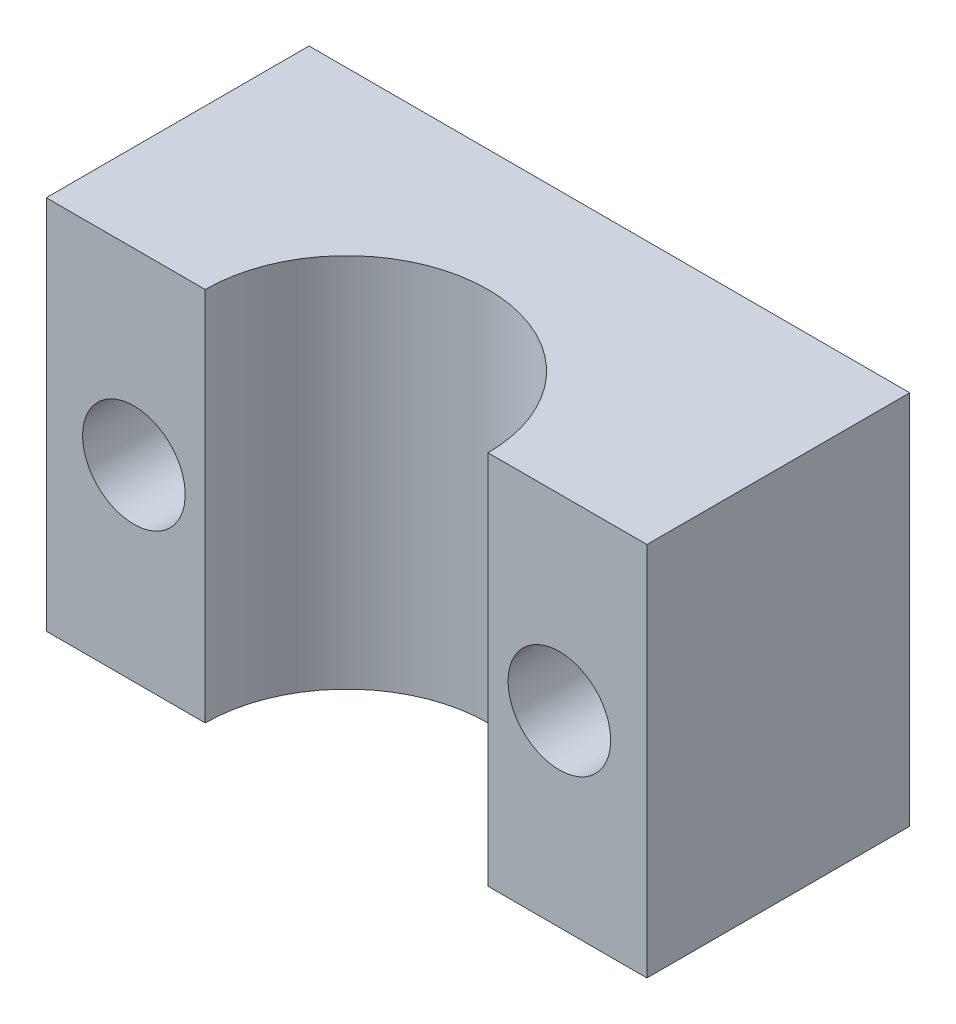
SolidWorks part; units mm, degrees
ref_plane "Спереди" through (0, 0, 0) normal (0, 0, 1) x (1, 0, 0)
ref_plane "Сверху" through (0, 0, 0) normal (0, 1, 0) x (1, 0, 0)
ref_plane "Справа" through (0, 0, 0) normal (1, 0, 0) x (0, 0, -1)
sketch "Эскиз1" plane through (0, 0, 0) normal (0, 1, 0) x (1, 0, 0)
  line L1 (-24, -10) -> (24, -10)
  line L2 (-24, -10) -> (-24, 10)
  line L3 (-24, 10) -> (24, 10)
  line L4 (24, -10) -> (24, 10)
  line L5 (-24, -10) -> (24, 10) construction
  line L6 (-24, 10) -> (24, -10) construction
  point P0 (0, 0)
  dimension "D1" = 48
  dimension "D2" = 20
extrude "Бобышка-Вытянуть1" add sketch "Эскиз1" along normal blind 30
sketch "Эскиз2" plane through (0, 0, 10) normal (0, 0, 1) x (1, 0, 0)
  line L0 (-7, 30) -> (-7, 0)
  line L1 (-24, 30) -> (24, 30) construction
  line L2 (-24, 0) -> (24, 0) construction
  line L3 (-7, 0) -> (7, 0)
  line L4 (7, 0) -> (7, 30)
  line L5 (7, 30) -> (-7, 30)
  dimension "D1" = 17
  dimension "D2" = 14
extrude "Вырез-Вытянуть1" cut sketch "Эскиз2" against normal blind 7
sketch "Эскиз7" plane through (24, 0, 0) normal (1, 0, 0) x (0, 0, -1)
  line L1 (32, 30) -> (32, 0)
  line L2 (32, 0) -> (10, 0)
  line L3 (-10, 0) -> (10, 0)
  line L4 (10, 0) -> (10.066, 0.2736)
  line L5 (10, 30) -> (32, 30)
  line L8 (10, 0) -> (10, 30)
  dimension "D3" = 22
extrude "Бобышка-Вытянуть2" add sketch "Эскиз7" against normal blind 48
sketch "Эскиз8" plane through (24, 0, 0) normal (1, 0, 0) x (0, 0, -1)
  line L0 (11, 0) -> (11, 30)
  line L1 (-10, 30) -> (32, 30) construction
  line L2 (11, 30) -> (32, 30)
  line L3 (11, 0) -> (32, 0)
  line L4 (32, 0) -> (32, 30)
  line L5 (-10, 0) -> (32, 0) construction
  point P16 (11, 0)
extrude "Вырез-Вытянуть2" cut sketch "Эскиз8" against normal blind 14
sketch "Эскиз9" plane through (-24, 0, 0) normal (-1, 0, 0) x (0, 0, 1)
  line L0 (-11, 0) -> (-11, 30)
  line L1 (-32, 30) -> (10, 30) construction
  line L2 (-11, 30) -> (-32, 30)
  line L3 (-32, 0) -> (10, 0) construction
  line L4 (-11, 0) -> (-32, 0)
  line L5 (-32, 0) -> (-32, 30)
  point P15 (-11, 0)
extrude "Вырез-Вытянуть3" cut sketch "Эскиз9" against normal blind 14
sketch "Эскиз11" plane through (-10, 0, 0) normal (-1, 0, 0) x (0, 0, 1)
  line L0 (-32, 30) -> (-11, 0) construction
  line L2 (-32, 0) -> (-11, 0) construction
  line L3 (-16.4, 4.9) -> (-16.4, 25.1)
  line L6 (-16.4, 4.9) -> (-26.6, 4.9)
  line L7 (-16.4, 25.1) -> (-26.6, 25.1)
  line L8 (-26.6, 4.9) -> (-26.6, 25.1)
  line L9 (-16.4, 4.9) -> (-26.6, 25.1) construction
  line L10 (-16.4, 25.1) -> (-26.6, 4.9) construction
  point P7 (-21.5, 15)
  point P8 (-21.5, 15)
  dimension "D1" = 20.2
  dimension "D2" = 10.2
extrude "Вырез-Вытянуть4" cut sketch "Эскиз11" against normal through all
sketch "Эскиз13" plane through (0, 0, -11) normal (0, 0, -1) x (-1, 0, 0)
  line L0 (24, 15) -> (10, 15) construction
  line L1 (24, 0) -> (24, 30) construction
  line L2 (10, 0) -> (10, 30) construction
  line L3 (-10, 15) -> (-24, 15) construction
  line L4 (-10, 30) -> (-10, 0) construction
  line L5 (-24, 30) -> (-24, 0) construction
  circle A0 centre (17, 15) radius 4.1
  circle A1 centre (-17, 15) radius 4.1
  dimension "D1" = 8.2
extrude "Вырез-Вытянуть5" cut sketch "Эскиз13" against normal through all
fillet "Скругление1" radius 7 2 edges at (-7, 15, 3) (7, 15, 3)
sketch "Sketch1" plane through (10, 0, 0) normal (1, 0, 0) x (0, 0, -1)
  line L0 (16.4, 25.1) -> (26.6, 4.9) construction
  line L2 (26.6, 4.9) -> (16.4, 4.9)
  line L3 (26.6, 4.9) -> (26.6, 25.1)
  line L4 (26.6, 25.1) -> (16.4, 25.1)
  line L5 (16.4, 4.9) -> (16.4, 25.1)
  line L6 (26.6, 4.9) -> (16.4, 25.1) construction
  line L7 (26.6, 25.1) -> (16.4, 4.9) construction
  point P4 (21.5, 15)
extrude "Boss-Extrude1" add sketch "Sketch1" against normal blind 4
sketch "Sketch2" plane through (0, 30, 0) normal (0, 1, 0) x (1, 0, 0)
  line L0 (-10, 11) -> (10, 32) construction
  line L2 (-10, 32) -> (10, 32)
  line L3 (-10, 32) -> (-10, 11)
  line L4 (-10, 11) -> (10, 11)
  line L5 (10, 32) -> (10, 11)
  line L6 (-10, 32) -> (10, 11) construction
  line L7 (-10, 11) -> (10, 32) construction
  point P4 (0, 21.5)
extrude "Cut-Extrude1" cut sketch "Sketch2" against normal through all
sketch "Sketch3" plane through (0, 30, 0) normal (0, 1, 0) x (1, 0, 0)
  line L0 (7, -10) -> (-7, -10) construction
  circle A0 centre (0, -10) radius 11.3
  dimension "D1" = 22.6
extrude "Cut-Extrude2" cut sketch "Sketch3" against normal through all
